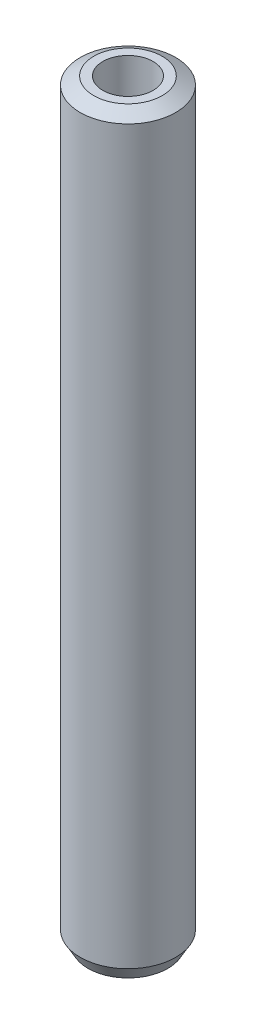
SolidWorks part; units mm, degrees
ref_plane "Front Plane" through (0, 0, 0) normal (0, 0, 1) x (1, 0, 0)
ref_plane "Top Plane" through (0, 0, 0) normal (0, 1, 0) x (1, 0, 0)
ref_plane "Right Plane" through (0, 0, 0) normal (1, 0, 0) x (0, 0, -1)
sketch "Sketch1" plane through (0, 0, 0) normal (0, 1, 0) x (1, 0, 0)
  circle A0 centre (0, 0) radius 25
  dimension "SHAFT_OD" = 50
extrude "Boss-Extrude1" add sketch "Sketch1" along normal blind 394.2087
sketch "Sketch2" plane through (0, 0, 0) normal (0, 1, 0) x (1, 0, 0)
  circle A0 centre (0, 0) radius 13.1578
  dimension "BORE_D" = 26.3156
extrude "Cut-Extrude1" cut sketch "Sketch2" along normal through all
chamfer "Chamfer1" distance 4.0981 angle 60 2 edges at (0, 394.2087, 25) (0, 0, 25) first distance on face at (0, 394.2087, 25) first distance on face at (0, 0, 13.1578)
